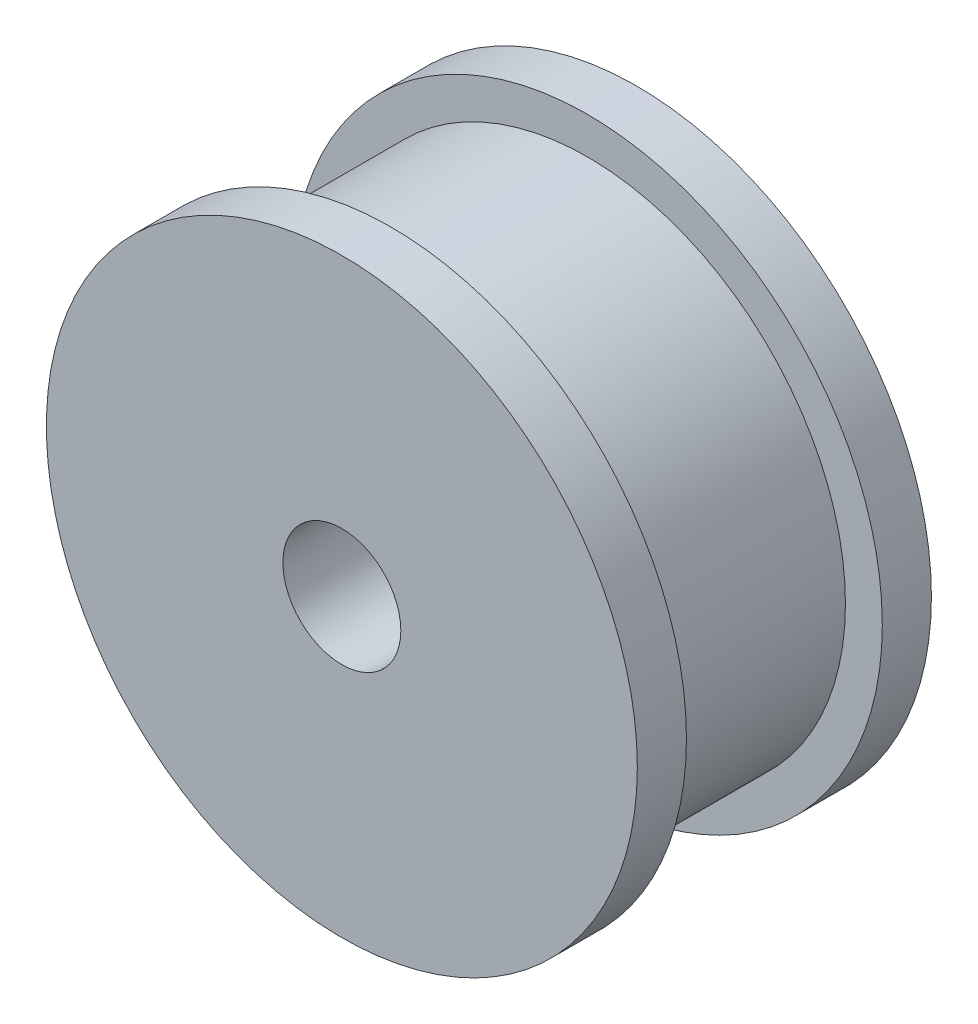
SolidWorks part; units mm, degrees
ref_plane "Plano frontal" through (0, 0, 0) normal (0, 0, 1) x (1, 0, 0)
ref_plane "Plano superior" through (0, 0, 0) normal (0, 1, 0) x (1, 0, 0)
ref_plane "Plano direito" through (0, 0, 0) normal (1, 0, 0) x (0, 0, -1)
sketch "Esboço1" plane through (0, 0, 0) normal (0, 0, 1) x (1, 0, 0)
  circle A0 centre (0, 0) radius 10.5
  circle A1 centre (0, 0) radius 2.4
  dimension "D1" = 21
  dimension "D2" = 4.8
extrude "Ressalto-extrusão1" add sketch "Esboço1" along normal blind 8
sketch "Esboço2" plane through (0, 0, 0) normal (0, 0, 1) x (1, 0, 0)
  circle A0 centre (0, 0) radius 12
  circle A1 centre (0, 0) radius 2.4
  dimension "D1" = 24
extrude "Ressalto-extrusão2" add sketch "Esboço2" against normal blind 2
sketch3d "3DSketch2"
  circle A0 centre (0, 0, 8) radius 2.4
  circle A1 centre (0, 0, 8) radius 12.0279
  point P2 (0, 0, 10.4)
  point P5 (0, 0, 20.0279)
extrude "Ressalto-extrusão3" add sketch "3DSketch2" along direction (0, 0, 1) on the side of the normal blind 2
